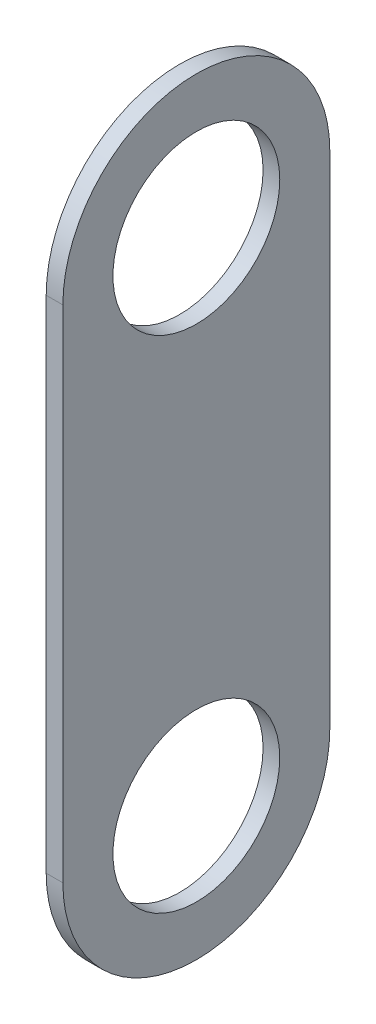
SolidWorks part; units mm, degrees
material "Wrought Stainless Steel"
ref_plane "Front Plane" through (0, 0, 0) normal (0, 0, 1) x (1, 0, 0)
ref_plane "Top Plane" through (0, 0, 0) normal (0, 1, 0) x (1, 0, 0)
ref_plane "Right Plane" through (0, 0, 0) normal (1, 0, 0) x (0, 0, -1)
sketch "Sketch1" plane through (0, 0, 0) normal (1, 0, 0) x (0, 0, -1)
  line L0 (0, -7.5) -> (0, 7.5) construction
  line L5 (-4, -7.5) -> (-4, 7.5)
  line L6 (4, -7.5) -> (4, 7.5)
  arc A0 (-4, -7.5) -> (4, -7.5) centre (0, -7.5) ccw
  arc A1 (4, 7.5) -> (-4, 7.5) centre (0, 7.5) ccw
  circle A2 centre (0, 7.5) radius 2.5
  circle A3 centre (0, -7.5) radius 2.5
  point P2 (0, 0)
  dimension "D2" = 5
  dimension "D3" = 4
  dimension "D1" = 15
base flange "Base-Flange1" sketch "Sketch1" thickness 0.5 reverse thickness direction no parameters "D1"=0.5
sketch "Bend-Lines1" [suppressed] plane through (0, 0, 0) normal (0, 1, 0) x (1, 0, 0)
sketch "Bounding-Box1" [suppressed] plane through (0, 0, 0) normal (0, 1, 0) x (1, 0, 0)
sheet metal parameters "Sheet-Metal1" thickness 0.5 parameters "D1"=0.5
flat pattern "Flat-Pattern1" [suppressed]
sketch "Bend-Lines2" plane through (0, 0, 0) normal (0, 1, 0) x (1, 0, 0)
sketch3d "Bounding-Box2" [suppressed]
  line L0 (-4, 19, 0) -> (-4, -4, 0) construction
  line L1 (4, 19, 0) -> (4, -4, 0) construction
  line L2 (-4, 19, 0) -> (4, 19, 0) construction
  line L3 (-4, -4, 0) -> (4, -4, 0) construction
